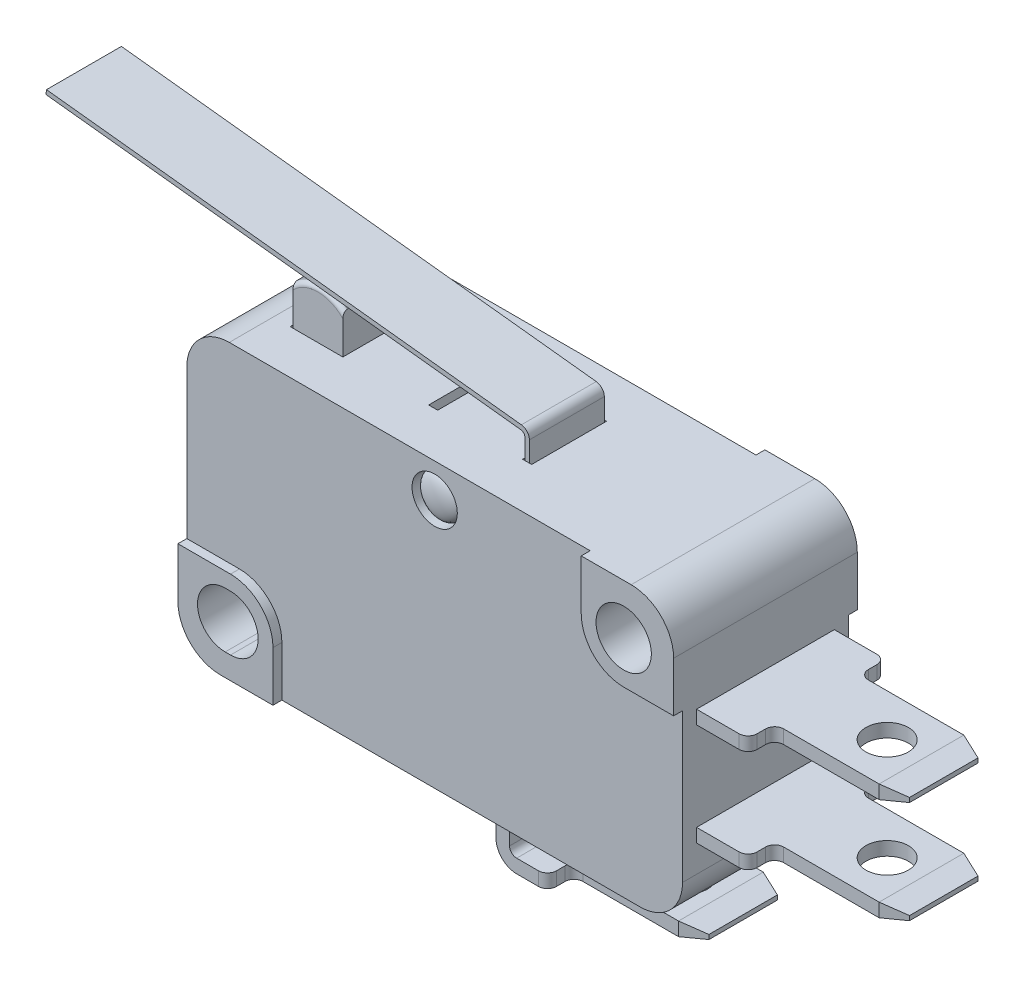
SolidWorks part; units mm, degrees
ref_plane "Front Plane" through (0, 0, 0) normal (0, 0, 1) x (1, 0, 0)
ref_plane "Top Plane" through (0, 0, 0) normal (0, 1, 0) x (1, 0, 0)
ref_plane "Right Plane" through (0, 0, 0) normal (1, 0, 0) x (0, 0, -1)
sketch "Sketch1" plane through (0, 0, 0) normal (0, 0, 1) x (1, 0, 0)
  line L0 (-11.25, -5.15) -> (-10.95, -5.15) construction
  line L1 (-13.9, 7.95) -> (13.9, 7.95) construction
  line L2 (-13.9, 7.95) -> (-13.9, -7.95) construction
  line L3 (-13.9, -7.95) -> (13.9, -7.95) construction
  line L4 (13.9, 7.95) -> (13.9, -7.95) construction
  line L5 (0, -7.95) -> (0, 7.95) construction
  line L6 (-13.9, 0) -> (13.9, 0) construction
  line L7 (-11.25, -3.6) -> (-10.95, -3.6) construction
  line L8 (-11.25, -6.7) -> (-10.95, -6.7) construction
  line L9 (13.9, -4.05) -> (22.65, -4.05) construction
  line L10 (22.65, -4.05) -> (23.9, -3.794) construction
  line L11 (23.9, -3.794) -> (23.9, -3.544) construction
  line L12 (23.9, -3.544) -> (22.65, -3.288) construction
  line L13 (22.65, -3.288) -> (13.9, -3.288) construction
  line L14 (13.9, 1.688) -> (22.65, 1.688) construction
  line L15 (22.65, 1.688) -> (23.9, 1.944) construction
  line L16 (23.9, 1.944) -> (23.9, 2.194) construction
  line L17 (23.9, 2.194) -> (22.65, 2.45) construction
  line L18 (22.65, 2.45) -> (13.9, 2.45) construction
  line L19 (3.412, -7.95) -> (3.412, -9.83) construction
  line L20 (3.412, -9.83) -> (11.4, -9.83) construction
  line L21 (11.4, -9.83) -> (12.65, -10.086) construction
  line L22 (12.65, -10.086) -> (12.65, -10.336) construction
  line L23 (12.65, -10.336) -> (11.4, -10.592) construction
  line L24 (11.4, -10.592) -> (2.65, -10.592) construction
  line L25 (2.65, -10.592) -> (2.65, -7.95) construction
  line L26 (3.412, -7.95) -> (2.65, -7.95) construction
  line L27 (13.9, 2.45) -> (13.9, 1.688) construction
  line L28 (13.9, -3.288) -> (13.9, -4.05) construction
  line L29 (2.65, -10.592) -> (2.65, -9.83) construction
  line L30 (2.65, -10.211) -> (12.65, -10.211) construction
  line L31 (13.9, -3.669) -> (23.9, -3.669) construction
  line L32 (13.9, 2.069) -> (23.9, 2.069) construction
  line L33 (-10.5, 7.95) -> (-10.5, 9.55) construction
  line L34 (-10.5, 9.55) -> (-7.7, 9.55) construction
  line L35 (-7.7, 9.55) -> (-7.7, 7.95) construction
  line L36 (-2.3813, 7.95) -> (2.3813, 7.95) construction
  line L37 (2.3813, 7.95) -> (2.8892, 7.95) construction
  line L38 (2.6353, 7.95) -> (2.6353, 9.423) construction
  line L39 (2.6353, 9.423) -> (-24.3336, 12.4238) construction
  line L40 (2.6353, 9.423) -> (-24.5, 9.423) construction
  line L41 (-24.5, 9.296) -> (-24.5, 9.55) construction
  line L42 (-24.3195, 12.55) -> (-24.3476, 12.2976) construction
  circle A0 centre (11.1, 5.15) radius 1.55 construction
  arc A1 (-11.25, -3.6) -> (-11.25, -6.7) centre (-11.25, -5.15) ccw construction
  arc A2 (-10.95, -6.7) -> (-10.95, -3.6) centre (-10.95, -5.15) ccw construction
  point P0 (0, 0)
  point P11 (-11.1, -5.15)
  point P16 (-12.8, -5.15)
  point P17 (-9.4, -5.15)
  point P46 (-9.1, 9.55)
  point P48 (-9.1, 12.55)
  point P50 (-9.1, 10.3)
  point P52 (0, 7.95)
  point P57 (-9.1, 7.39)
  point P59 (2.6352, 7.95)
  point P60 (-2.3813, 7.95)
  point P61 (2.3812, 7.95)
  point P62 (2.8892, 7.95)
  point P68 (-24.5, 9.423)
  point P71 (-24.3336, 12.4238)
  point P78 (2.6353, 7.95)
  dimension "D1" = 3.1
  dimension "Mounting Hole Diameter" = 3.1
  dimension "D20" = 35.6
  dimension "D2" = 3.4
  dimension "Housing Height" = 15.9
  dimension "Housing Length" = 27.8
  dimension "D3" = 10.3
  dimension "D4" = 2.8
  dimension "D5" = 22.2
  dimension "D6" = 2.8
  dimension "D7" = 10
  dimension "D8" = 17.78
  dimension "D9" = 1.25
  dimension "D10" = 0.762
  dimension "D11" = 0.25
  dimension "D12" = 2.8
  dimension "D13" = 20.2
  dimension "D14" = 14.7
  dimension "D15" = 6.5
  dimension "Actuation Travel" = 3
  dimension "D16" = 5.5
  dimension "Actuator Height" = 4.6
  dimension "Over Travel" = 2.16
  dimension "Deactuation Travel" = 0.75
  dimension "D17" = 4.7625
  dimension "D18" = 0.508
  dimension "D19" = 0.254
sketch "Sketch2" plane through (0, 0, 0) normal (1, 0, 0) x (0, 0, -1)
  line L0 (-2.3749, -10.211) -> (2.3749, -10.211) construction
  line L1 (5.15, 0) -> (-5.15, 0) construction
  line L3 (2.1, 12.55) -> (-2.1, 12.55) construction
  point P3 (0, -10.211)
  point P8 (0, 0)
  point P12 (0, 12.55)
  dimension "Quick Disconnect Tab Width" = 4.7498
  dimension "D1" = 4.2
  dimension "Housing Depth" = 10.3
sketch "Sketch3" plane through (0, 0, 0) normal (0, 0, 1) x (1, 0, 0)
  line L0 (-11.25, -5.15) -> (-10.95, -5.15) construction
  line L1 (-11.5187, 7.95) -> (11.5187, 7.95)
  line L2 (-13.9, 5.5687) -> (-13.9, -5.5687)
  line L3 (-11.5187, -7.95) -> (11.5187, -7.95)
  line L4 (13.9, 5.5687) -> (13.9, -5.5687)
  line L5 (0, -7.95) -> (0, 7.95) construction
  line L6 (-13.9, 0) -> (13.9, 0) construction
  line L7 (-11.25, -3.6) -> (-10.95, -3.6)
  line L8 (-11.25, -6.7) -> (-10.95, -6.7)
  arc A0 (-13.9, -5.5687) -> (-11.5187, -7.95) centre (-11.5188, -5.5688) ccw
  arc A1 (11.5187, -7.95) -> (13.9, -5.5687) centre (11.5188, -5.5688) ccw
  arc A2 (11.5187, 7.95) -> (13.9, 5.5687) centre (11.5188, 5.5688) cw
  arc A3 (-11.5187, 7.95) -> (-13.9, 5.5687) centre (-11.5188, 5.5688) ccw
  circle A4 centre (11.1, 5.15) radius 1.55
  arc A5 (-11.25, -3.6) -> (-11.25, -6.7) centre (-11.25, -5.15) ccw
  arc A6 (-10.95, -6.7) -> (-10.95, -3.6) centre (-10.95, -5.15) ccw
  circle A7 centre (11.1, 5.15) radius 1.55 construction
  point P10 (13.9, -7.95)
  point P15 (-13.9, 7.95)
  point P20 (-11.1, -5.15)
  point P44 (0, 0)
  dimension "D1" = 2.3813
extrude "Boss-Extrude1" add sketch "Sketch3" along normal up to vertex (5.15 mm away) and the other way up to vertex (5.15 mm away) up to point (0, 0, 5.15) other way up to point (0, 0, -5.15)
sketch "Sketch4" plane through (0, 0, 0) normal (0, 0, 1) x (1, 0, 0)
  line L0 (-13.9, -2.7688) -> (-10.95, -2.7688)
  line L1 (-13.9, 7.95) -> (-13.9, -7.95) construction
  line L2 (-8.5687, -5.15) -> (-8.5687, -7.95)
  line L3 (-13.9, -7.95) -> (13.9, -7.95) construction
  line L4 (-8.5687, -7.95) -> (13.9, -7.95)
  line L5 (13.9, -7.95) -> (13.9, 2.7688)
  line L6 (13.9, 7.95) -> (13.9, -7.95) construction
  line L7 (13.9, 2.7688) -> (11.1, 2.7688)
  line L8 (8.7188, 5.15) -> (8.7188, 7.95)
  line L9 (-13.9, 7.95) -> (13.9, 7.95) construction
  line L10 (8.7188, 7.95) -> (-13.9, 7.95)
  line L11 (-13.9, 7.95) -> (-13.9, -2.7688)
  arc A0 (11.1, 2.7688) -> (8.7188, 5.15) centre (11.1, 5.15) cw
  arc A1 (-10.95, -2.7688) -> (-8.5687, -5.15) centre (-10.95, -5.15) cw
  circle A2 centre (11.1, 5.15) radius 1.55 construction
  arc A3 (-10.95, -6.7) -> (-10.95, -3.6) centre (-10.95, -5.15) ccw construction
  dimension "D1" = 2.3813
extrude "Cut-Extrude1" cut sketch "Sketch4" against normal blind 0.5 from surface starting at face at (0, 0, 5.15)
mirror "Mirror1" about plane through (0, 0, 0) normal (0, 0, 1) of "Cut-Extrude1"
sketch "Sketch10" plane through (0, 0, 0) normal (0, 0, 1) x (1, 0, 0)
  line L0 (-2.3813, 7.95) -> (2.3813, 7.95) construction
  line L1 (-2.8893, 7.95) -> (-2.3813, 7.95)
  line L2 (-2.8893, 7.95) -> (-2.8892, 6.3625)
  line L3 (-2.8892, 6.3625) -> (-2.3813, 6.3625)
  line L4 (-2.3813, 7.95) -> (-2.3813, 6.3625)
  line L5 (-2.6352, 6.3625) -> (-2.6352, 7.95) construction
  line L6 (-2.8893, 7.1562) -> (-2.3813, 7.1562) construction
  line L7 (2.3813, 7.95) -> (2.8893, 7.95)
  line L8 (2.3813, 7.95) -> (2.3813, 6.3625)
  line L9 (2.3813, 6.3625) -> (2.8892, 6.3625)
  line L10 (2.8893, 7.95) -> (2.8892, 6.3625)
  line L11 (2.6352, 6.3625) -> (2.6352, 7.95) construction
  line L12 (2.3813, 7.1562) -> (2.8893, 7.1562) construction
  point P10 (0, 7.95)
  point P42 (2.6353, 7.1562)
  point P88 (-2.6353, 7.1562)
  dimension "D2" = 1.5875
extrude "Cut-Extrude5" cut sketch "Sketch10" against normal up to vertex (2.1 mm away) and the other way up to vertex (2.1 mm away) up to point (0, 12.55, -2.1) other way up to point (0, 12.55, 2.1)
sketch "Sketch8" plane through (0, 0, 0) normal (0, 0, 1) x (1, 0, 0)
  line L0 (-13.9, 7.95) -> (13.9, 7.95) construction
  line L1 (-10.5762, 7.95) -> (-7.6238, 7.95)
  line L2 (-10.5762, 7.95) -> (-10.5762, 7.5531)
  line L3 (-10.5762, 7.5531) -> (-7.6238, 7.5531)
  line L4 (-7.6238, 7.95) -> (-7.6238, 7.5531)
  line L5 (-9.1, 7.5531) -> (-9.1, 7.95) construction
  line L6 (-10.5762, 7.7516) -> (-7.6238, 7.7516) construction
  line L7 (-7.7, 9.55) -> (-7.7, 7.95) construction
  point P36 (-9.1, 7.7516)
  dimension "D1" = 0.0762
  dimension "D2" = 0.3969
extrude "Cut-Extrude4" cut sketch "Sketch8" against normal mid plane 4.3524
sketch "Sketch9" plane through (0, 0, 0) normal (0, 0, 1) x (1, 0, 0)
  line L0 (-10.5, 10.0795) -> (-10.5, 7.5531)
  line L1 (-10.5762, 7.5531) -> (-7.6238, 7.5531) construction
  line L2 (-10.5, 7.5531) -> (-7.7, 7.5531)
  line L3 (-7.7, 7.5531) -> (-7.7, 10.0795)
  line L4 (-7.7, 9.55) -> (-10.5, 9.55) construction
  line L5 (-10.5, 7.95) -> (-10.5, 9.55) construction
  line L6 (-7.7, 9.55) -> (-7.7, 7.95) construction
  line L7 (-24.3476, 12.2976) -> (-8.8586, 10.5741) construction
  line L8 (2.6353, 9.423) -> (-24.3336, 12.4238) construction
  arc A0 (-10.5, 10.0795) -> (-7.7, 10.0795) centre (-9.1, 8.4044) cw
  dimension "D1" = 2.1831
extrude "Boss-Extrude3" add sketch "Sketch9" against normal up to vertex (2.1 mm away) and the other way up to vertex (2.1 mm away) separate body up to point (0, 12.55, -2.1) other way up to point (0, 12.55, 2.1)
sketch "Sketch5" plane through (0, 0, 0) normal (0, 0, 1) x (1, 0, 0)
  line L0 (13.9, 1.688) -> (13.9, 2.45)
  line L1 (13.9, 2.45) -> (22.65, 2.45)
  line L2 (22.65, 2.45) -> (23.9, 2.194)
  line L3 (23.9, 2.194) -> (23.9, 1.944)
  line L4 (23.9, 1.944) -> (22.65, 1.688)
  line L5 (22.65, 1.688) -> (13.9, 1.688)
  line L6 (13.9, -3.288) -> (22.65, -3.288)
  line L7 (22.65, -3.288) -> (23.9, -3.544)
  line L8 (23.9, -3.544) -> (23.9, -3.794)
  line L9 (23.9, -3.794) -> (22.65, -4.05)
  line L10 (22.65, -4.05) -> (13.9, -4.05)
  line L11 (13.9, -4.05) -> (13.9, -3.288)
  line L12 (2.65, -7.95) -> (2.65, -9.4331)
  line L13 (3.8089, -10.592) -> (11.4, -10.592)
  line L14 (11.4, -10.592) -> (12.65, -10.336)
  line L15 (12.65, -10.336) -> (12.65, -10.086)
  line L16 (12.65, -10.086) -> (11.4, -9.83)
  line L17 (11.4, -9.83) -> (3.8089, -9.83)
  line L18 (3.412, -9.4331) -> (3.412, -7.95)
  line L19 (3.412, -7.95) -> (2.65, -7.95)
  line L20 (11.4, -9.83) -> (12.65, -9.83) construction
  line L21 (12.65, -9.83) -> (12.65, -10.086) construction
  line L22 (11.4, -10.592) -> (12.65, -10.592) construction
  line L23 (12.65, -10.592) -> (12.65, -10.336) construction
  line L24 (22.65, 2.45) -> (23.9, 2.45) construction
  line L25 (23.9, 2.45) -> (23.9, 2.194) construction
  line L26 (22.65, 1.688) -> (23.9, 1.688) construction
  line L27 (23.9, 1.688) -> (23.9, 1.944) construction
  line L28 (22.65, -3.288) -> (23.9, -3.288) construction
  line L29 (23.9, -3.288) -> (23.9, -3.544) construction
  line L30 (22.65, -4.05) -> (23.9, -4.05) construction
  line L31 (23.9, -4.05) -> (23.9, -3.794) construction
  arc A0 (2.65, -9.4331) -> (3.8089, -10.592) centre (3.8089, -9.4331) ccw
  arc A1 (3.8089, -9.83) -> (3.412, -9.4331) centre (3.8089, -9.4331) cw
  point P42 (2.65, -10.592)
  point P45 (3.412, -9.83)
  dimension "D2" = 0.3969
extrude "Boss-Extrude2" add sketch "Sketch5" along normal mid plane 7.725 separate body
sketch "Sketch23" plane through (0, 0, 0) normal (0, 0, 1) x (1, 0, 0)
  line L6 (2.2823, 9.3345) -> (-24.3476, 12.2976)
  line L8 (-24.3476, 12.2976) -> (-24.3195, 12.55)
  line L9 (-24.3195, 12.55) -> (2.3104, 9.5869)
  line L10 (2.7623, 9.082) -> (2.7622, 6.3625)
  line L11 (2.7622, 6.3625) -> (2.5082, 6.3625)
  line L12 (2.5082, 6.3625) -> (2.5083, 9.082)
  arc A4 (2.2823, 9.3345) -> (2.5083, 9.082) centre (2.2543, 9.082) cw
  arc A5 (2.3104, 9.5869) -> (2.7623, 9.082) centre (2.2543, 9.082) cw
  point P5 (2.6352, 6.3625)
  dimension "D1" = 0.254
extrude "Boss-Extrude9" add sketch "Sketch23" along normal up to surface and the other way up to surface separate body up to face at (-9.1, 8.9433, 2.1) other way up to face at (-9.1, 8.9433, -2.1)
fillet "Fillet5" radius 0.254 2 edges at (-9.1, 10.5875, 2.1) (-9.1, 10.5875, -2.1)
sketch "Sketch6" plane through (0, 0, 0) normal (0, 1, 0) x (1, 0, 0)
  line L0 (13.9, 3.8625) -> (13.9, -3.8625)
  line L1 (13.9, -3.8625) -> (16.2813, -3.8625)
  line L2 (16.7893, -3.3545) -> (16.7893, -2.8829)
  line L3 (17.2973, -2.3749) -> (22.65, -2.3749)
  line L4 (22.65, -2.3749) -> (23.9, -1.9199)
  line L5 (23.9, -1.9199) -> (23.9, 1.9199)
  line L6 (23.9, 1.9199) -> (22.65, 2.3749)
  line L7 (22.65, 2.3749) -> (17.2973, 2.3749)
  line L8 (16.7893, 2.8829) -> (16.7893, 3.3545)
  line L9 (16.2813, 3.8625) -> (13.9, 3.8625)
  line L10 (20.725, 0) -> (23.9, 0) construction
  line L12 (13.9, 0) -> (22.65, 0) construction
  circle A0 centre (20.725, 0) radius 1.1906
  arc A1 (16.2813, -3.8625) -> (16.7893, -3.3545) centre (16.2813, -3.3545) ccw
  arc A2 (16.7893, -2.8829) -> (17.2973, -2.3749) centre (17.2973, -2.8829) cw
  arc A3 (17.2973, 2.3749) -> (16.7893, 2.8829) centre (17.2973, 2.8829) cw
  arc A4 (16.7893, 3.3545) -> (16.2813, 3.8625) centre (16.2813, 3.3545) ccw
  point P11 (13.9, 0)
  dimension "D1" = 20
  dimension "D2" = 2.3813
  dimension "D4" = 0.508
  dimension "D3" = 3.175
  dimension "D5" = 2.3813
extrude "Cut-Extrude2" cut sketch "Sketch6" against normal through all both and the other way through all flip side to cut
sketch "Sketch7" plane through (0, 0, 0) normal (0, 1, 0) x (1, 0, 0)
  line L0 (2.65, 3.8625) -> (2.65, -3.8625)
  line L1 (2.65, -3.8625) -> (5.0312, -3.8625)
  line L2 (5.5392, -3.3545) -> (5.5392, -2.8829)
  line L3 (6.0472, -2.3749) -> (11.4, -2.3749)
  line L4 (11.4, -2.3749) -> (12.65, -1.9199)
  line L5 (12.65, -1.9199) -> (12.65, 1.9199)
  line L6 (12.65, 1.9199) -> (11.4, 2.3749)
  line L7 (11.4, 2.3749) -> (6.0472, 2.3749)
  line L8 (5.5392, 2.8829) -> (5.5392, 3.3545)
  line L9 (5.0312, 3.8625) -> (2.65, 3.8625)
  line L10 (13.9, 3.8625) -> (13.9, -3.8625) construction
  line L11 (23.9, -1.9199) -> (23.9, 1.9199) construction
  line L12 (2.65, 0) -> (12.65, 0) construction
  line L13 (23.9, 1.9199) -> (22.65, 2.3749) construction
  line L14 (22.65, -2.3749) -> (23.9, -1.9199) construction
  line L15 (22.65, 2.3749) -> (17.2973, 2.3749) construction
  circle A0 centre (9.475, 0) radius 1.1906
  arc A1 (5.0312, -3.8625) -> (5.5392, -3.3545) centre (5.0312, -3.3545) ccw
  arc A2 (5.5392, -2.8829) -> (6.0472, -2.3749) centre (6.0472, -2.8829) cw
  arc A3 (6.0472, 2.3749) -> (5.5392, 2.8829) centre (6.0472, 2.8829) cw
  arc A4 (5.5392, 3.3545) -> (5.0312, 3.8625) centre (5.0312, 3.3545) ccw
  dimension "D1" = 2.3813
  dimension "D3" = 0.508
  dimension "D2" = 3.175
extrude "Cut-Extrude3" cut sketch "Sketch7" against normal through all flip side to cut
sketch "Sketch25" plane through (0, 0, 4.65) normal (0, 0, 1) x (1, 0, 0)
  line L0 (0, -7.95) -> (0, 7.95) construction
  circle A0 centre (0, 6.045) radius 1.27
  dimension "D1" = 2.54
  dimension "D2" = 1.905
extrude "Cut-Extrude6" cut sketch "Sketch25" against normal blind 1.27
sketch "Sketch26" plane through (0, 0, 3.38) normal (0, 0, 1) x (1, 0, 0)
  circle A0 centre (0, 6.045) radius 1.2065
  dimension "D1" = 2.413
extrude "Boss-Extrude10" add sketch "Sketch26" along normal blind 0.762 separate body
dome "Dome1" faces to dome 1 distance 0.508 reverse direction no elliptical dome yes face at (1.2065, 6.045, 4.142) parameters "D1"=0.508
mirror "Mirror2" about plane through (0, 0, 0) normal (0, 0, 1) of "Cut-Extrude6"
mirror "Mirror3" about plane through (0, 0, 0) normal (0, 0, 1) of bodies 146
sketch "Sketch24" plane through (0, 0, 0) normal (0, 0, 1) x (1, 0, 0)
  line L0 (2.3911, 9.296) -> (-24.5, 9.296)
  line L1 (-24.5, 9.296) -> (-24.5, 9.55)
  line L2 (-24.5, 9.55) -> (0.3454, 9.55)
  line L3 (2.2823, 9.3345) -> (-24.3476, 12.2976) construction
  arc A0 (2.5083, 9.082) -> (2.2823, 9.3345) centre (2.2543, 9.082) ccw construction
equation "\"D1@Boss-Extrude2\"=\"Housing Depth@Sketch2\"*.75"
equation "\"D1@Cut-Extrude4\"=\"D1@Sketch2\"+.006"
